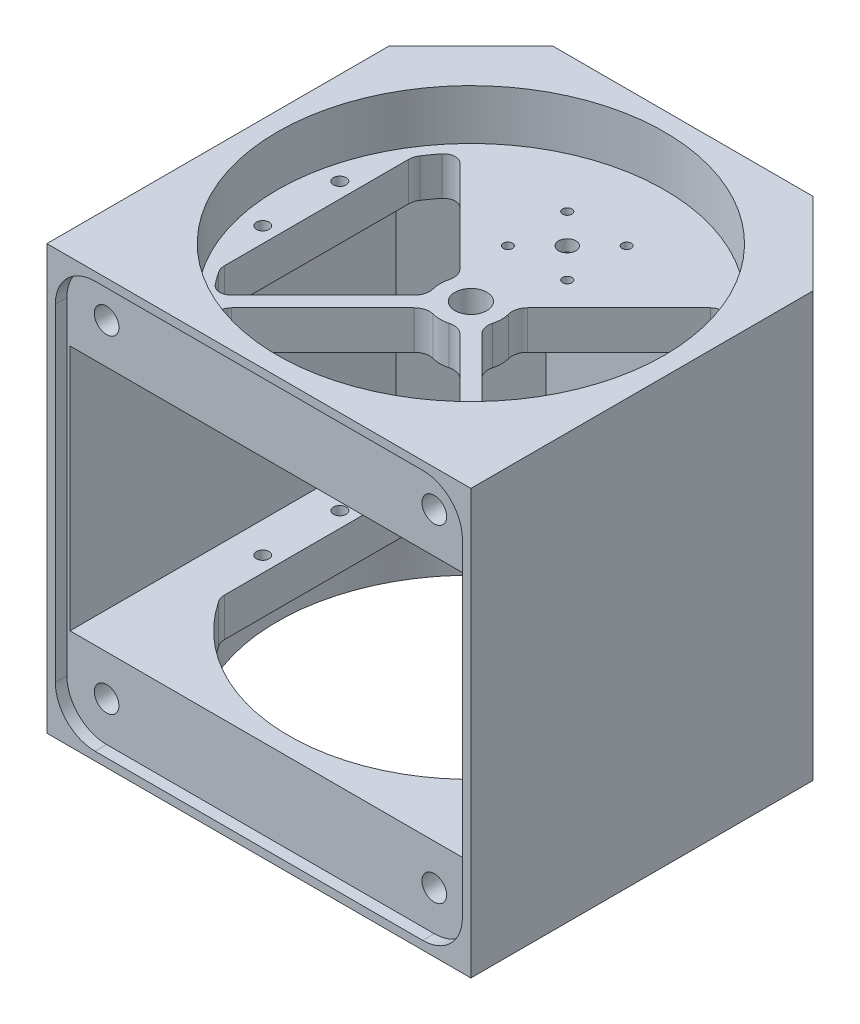
SolidWorks part; units mm, degrees
ref_plane "Front Plane" through (0, 0, 0) normal (0, 0, 1) x (1, 0, 0)
ref_plane "Top Plane" through (0, 0, 0) normal (0, 1, 0) x (1, 0, 0)
ref_plane "Right Plane" through (0, 0, 0) normal (1, 0, 0) x (0, 0, -1)
sketch "Sketch1" plane through (0, 0, 0) normal (0, 0, 1) x (1, 0, 0)
  line L5 (55, 55) -> (-55, 55)
  line L6 (55, 55) -> (55, -55)
  line L7 (55, -55) -> (-55, -55)
  line L12 (52.8, -42.5) -> (52.8, 42.5)
  line L13 (42.5, 52.8) -> (-42.5, 52.8)
  line L14 (-52.8, 42.5) -> (-52.8, -42.5)
  line L15 (-42.5, -52.8) -> (42.5, -52.8)
  line L16 (-55, 55) -> (-55, -55)
  line L17 (55, 55) -> (-55, -55) construction
  line L18 (55, -55) -> (-55, 55) construction
  arc A12 (52.8, 42.5) -> (42.5, 52.8) centre (42.5, 42.5) ccw
  arc A13 (-42.5, 52.8) -> (-52.8, 42.5) centre (-42.5, 42.5) ccw
  arc A14 (-52.8, -42.5) -> (-42.5, -52.8) centre (-42.5, -42.5) ccw
  arc A15 (42.5, -52.8) -> (52.8, -42.5) centre (42.5, -42.5) ccw
  point P0 (0, 0)
  dimension "D2" = 110
extrude "Boss-Extrude1" add sketch "Sketch1" against normal blind 3
sketch "Sketch2" plane through (0, -55, 0) normal (0, -1, 0) x (1, 0, 0)
  line L0 (55, -3) -> (55, -88.7868)
  line L1 (55, -88.7868) -> (33.7868, -110)
  line L2 (33.7868, -110) -> (-33.7868, -110)
  line L3 (-33.7868, -110) -> (-55, -88.7868)
  line L4 (-55, -88.7868) -> (-55, -3)
  line L5 (-55, -3) -> (55, -3) construction
  line L6 (-55, -3) -> (55, -3) construction
  line L7 (52, -3) -> (52, -87.5442)
  line L8 (-55, -3) -> (-55, 0) construction
  line L9 (-55, 0) -> (55, 0) construction
  line L10 (0, -110) -> (0, 0) construction
  line L11 (52, -87.5442) -> (32.5442, -107)
  line L12 (32.5442, -107) -> (-32.5442, -107)
  line L13 (-32.5442, -107) -> (-52, -87.5442)
  line L14 (-52, -87.5442) -> (-52, -3)
  line L15 (52, -3) -> (55, -3)
  line L16 (-55, -3) -> (-52, -3)
  circle A0 centre (0, -55) radius 50 construction
  dimension "D4" = 100
  dimension "D1" = 110
  dimension "D2" = 135
  dimension "D3" = 135
  dimension "D5" = 30
  dimension "D6" = 3
extrude "Boss-Extrude2" add sketch "Sketch2" against normal up to surface (110 mm away) up to face at (0, 55, -1.5)
sketch "Sketch3" plane through (0, -55, 0) normal (0, -1, 0) x (1, 0, 0)
  line L0 (-52, -3) -> (-52, -87.5442)
  line L1 (-52, -87.5442) -> (-32.5442, -107)
  line L2 (-32.5442, -107) -> (32.5442, -107)
  line L3 (32.5442, -107) -> (52, -87.5442)
  line L4 (52, -87.5442) -> (52, -3)
  line L5 (52, -3) -> (-52, -3)
  circle A0 centre (0, -55) radius 50.2
  dimension "D1" = 100.4
extrude "Boss-Extrude3" add sketch "Sketch3" against normal blind 3
sketch "Sketch4" plane through (0, -52, 0) normal (0, 1, 0) x (1, 0, 0)
  line L0 (11.2357, 3) -> (-11.2357, 3)
  circle A0 centre (0, 55) radius 50.2 construction
  circle A1 centre (0, 55) radius 50.2
  arc A2 (11.2357, 3) -> (-11.2357, 3) centre (0, 55) ccw
  circle A3 centre (0, 55) radius 53.2 construction
  dimension "D1" = 3
extrude "Boss-Extrude5" add sketch "Sketch4" along normal blind 10
sketch "Sketch5" plane through (0, -42, 0) normal (0, 1, 0) x (1, 0, 0)
  line L4 (52, 43.7643) -> (52, 66.2357)
  line L5 (11.2357, 107) -> (-11.2357, 107)
  line L6 (-52, 66.2357) -> (-52, 43.7643)
  line L7 (-11.2357, 3) -> (11.2357, 3)
  line L8 (52, 43.7643) -> (52, 66.2357)
  line L9 (11.2357, 107) -> (-11.2357, 107)
  line L10 (-52, 66.2357) -> (-52, 43.7643)
  line L11 (-11.2357, 3) -> (11.2357, 3)
  circle A0 centre (0, 55) radius 47.2
  circle A1 centre (0, 55) radius 50.2 construction
  arc A4 (11.2357, 3) -> (52, 43.7643) centre (0, 55) ccw
  arc A5 (52, 66.2357) -> (11.2357, 107) centre (0, 55) ccw
  arc A6 (-11.2357, 107) -> (-52, 66.2357) centre (0, 55) ccw
  arc A7 (-52, 43.7643) -> (-11.2357, 3) centre (0, 55) ccw
  arc A8 (11.2357, 3) -> (52, 43.7643) centre (0, 55) ccw
  arc A9 (52, 66.2357) -> (11.2357, 107) centre (0, 55) ccw
  arc A10 (-11.2357, 107) -> (-52, 66.2357) centre (0, 55) ccw
  arc A11 (-52, 43.7643) -> (-11.2357, 3) centre (0, 55) ccw
  dimension "D2" = 3
  dimension "D1" = 0
extrude "Boss-Extrude6" add sketch "Sketch5" along normal blind 2
sketch "Sketch11" plane through (0, -52, 0) normal (0, 1, 0) x (1, 0, 0)
  line L0 (-52, 43.7643) -> (-52, 3) construction
  line L1 (-52, 3) -> (-46.4799, 3) construction
  line L2 (-46.4799, 3) -> (-11.2357, 3) construction
  line L3 (-11.2357, 107) -> (-32.5442, 107) construction
  line L4 (-32.5442, 107) -> (-52, 87.5442) construction
  line L5 (-52, 87.5442) -> (-52, 66.2357) construction
  line L6 (52, 66.2357) -> (52, 87.5442) construction
  line L7 (52, 87.5442) -> (32.5442, 107) construction
  line L8 (32.5442, 107) -> (11.2357, 107) construction
  line L9 (11.2357, 3) -> (46.4799, 3) construction
  line L10 (46.4799, 3) -> (52, 3) construction
  line L11 (52, 3) -> (52, 43.7643) construction
  line L12 (-52, 43.7643) -> (-52, 3)
  line L13 (-52, 3) -> (-46.4799, 3)
  line L14 (-46.4799, 3) -> (-11.2357, 3)
  line L15 (-11.2357, 107) -> (-32.5442, 107)
  line L16 (-32.5442, 107) -> (-52, 87.5442)
  line L17 (-52, 87.5442) -> (-52, 66.2357)
  line L18 (52, 66.2357) -> (52, 87.5442)
  line L19 (52, 87.5442) -> (32.5442, 107)
  line L20 (32.5442, 107) -> (11.2357, 107)
  line L21 (11.2357, 3) -> (46.4799, 3)
  line L22 (46.4799, 3) -> (52, 3)
  line L23 (52, 3) -> (52, 43.7643)
  arc A0 (-52, 43.7643) -> (-11.2357, 3) centre (0, 55) ccw construction
  arc A1 (-11.2357, 107) -> (-52, 66.2357) centre (0, 55) ccw construction
  arc A2 (52, 66.2357) -> (11.2357, 107) centre (0, 55) ccw construction
  arc A3 (11.2357, 3) -> (52, 43.7643) centre (0, 55) ccw construction
  arc A4 (-52, 43.7643) -> (-11.2357, 3) centre (0, 55) ccw
  arc A5 (-11.2357, 107) -> (-52, 66.2357) centre (0, 55) ccw
  arc A6 (52, 66.2357) -> (11.2357, 107) centre (0, 55) ccw
  arc A7 (11.2357, 3) -> (52, 43.7643) centre (0, 55) ccw
extrude "Boss-Extrude14" add sketch "Sketch11" along normal blind 20
sketch "Sketch12" plane through (0, -40, 0) normal (0, 1, 0) x (1, 0, 0)
  line L4 (52, 43.7643) -> (52, 66.2357)
  line L5 (11.2357, 107) -> (-11.2357, 107)
  line L6 (-52, 66.2357) -> (-52, 43.7643)
  line L7 (-11.2357, 3) -> (11.2357, 3)
  line L8 (52, 43.7643) -> (52, 66.2357)
  line L9 (11.2357, 107) -> (-11.2357, 107)
  line L10 (-52, 66.2357) -> (-52, 43.7643)
  line L11 (-11.2357, 3) -> (11.2357, 3)
  circle A0 centre (0, 55) radius 47.2 construction
  circle A1 centre (0, 55) radius 47.2
  arc A4 (11.2357, 3) -> (52, 43.7643) centre (0, 55) ccw
  arc A5 (52, 66.2357) -> (11.2357, 107) centre (0, 55) ccw
  arc A6 (-11.2357, 107) -> (-52, 66.2357) centre (0, 55) ccw
  arc A7 (-52, 43.7643) -> (-11.2357, 3) centre (0, 55) ccw
  arc A8 (11.2357, 3) -> (52, 43.7643) centre (0, 55) ccw
  arc A9 (52, 66.2357) -> (11.2357, 107) centre (0, 55) ccw
  arc A10 (-11.2357, 107) -> (-52, 66.2357) centre (0, 55) ccw
  arc A11 (-52, 43.7643) -> (-11.2357, 3) centre (0, 55) ccw
  dimension "D1" = 0
extrude "Boss-Extrude16" add sketch "Sketch12" along normal up to surface (8 mm away) up to face at (38.445, -32, -93.445)
mirror "Mirror2" about plane through (0, 0, 0) normal (0, 1, 0) of "Boss-Extrude16", "Boss-Extrude14", "Boss-Extrude6", "Boss-Extrude5", "Boss-Extrude3"
sketch "Sketch13" plane through (0, 0, -3) normal (0, 0, 1) x (1, 0, 0)
  circle A0 centre (42.5, -42.5) radius 3.4195 construction
  circle A1 centre (-42.5, -42.5) radius 3.4195 construction
  circle A2 centre (-42.5, 42.5) radius 3.4195 construction
  circle A3 centre (42.5, 42.5) radius 3.4195 construction
  circle A4 centre (42.5, -42.5) radius 3.4195 construction
  circle A5 centre (-42.5, -42.5) radius 3.4195 construction
  circle A6 centre (-42.5, 42.5) radius 3.4195 construction
  circle A7 centre (42.5, 42.5) radius 3.4195 construction
  circle A8 centre (-42.5, 42.5) radius 3.2
  circle A9 centre (-42.5, -42.5) radius 3.2
  circle A10 centre (42.5, -42.5) radius 3.2
  circle A11 centre (42.5, 42.5) radius 3.2
  dimension "D1" = 6.4
extrude "Cut-Extrude2" cut sketch "Sketch13" against normal blind 15
sketch "Sketch14" plane through (0, 42, 0) normal (0, 1, 0) x (1, 0, 0)
  line L0 (0, 55) -> (0, -49945) construction
  line L1 (0, 55) -> (-35355.3391, 35410.3391) construction
  line L2 (0, 55) -> (35355.3391, 35410.3391) construction
  line L3 (-34.7597, 86.9313) -> (-6.8914, 59.063)
  line L4 (-31.9313, 89.7597) -> (-4.063, 61.8914)
  line L5 (-34.7597, 23.0687) -> (-6.8914, 50.937)
  line L6 (-4.063, 48.1086) -> (-31.9313, 20.2403)
  line L7 (6.8914, 50.937) -> (34.7597, 23.0687)
  line L8 (4.063, 48.1086) -> (31.9313, 20.2403)
  line L9 (4.063, 61.8914) -> (31.9313, 89.7597)
  line L10 (34.7597, 86.9313) -> (6.8914, 59.063)
  circle A0 centre (0, 55) radius 47.2 construction
  arc A1 (-34.7597, 23.0687) -> (-31.9313, 20.2403) centre (0, 55) ccw
  circle A2 centre (0, 55) radius 4.15
  arc A3 (-4.063, 48.1086) -> (4.063, 48.1086) centre (0, 55) ccw
  arc A4 (31.9313, 20.2403) -> (34.7597, 23.0687) centre (0, 55) ccw
  arc A5 (34.7597, 86.9313) -> (31.9313, 89.7597) centre (0, 55) ccw
  arc A6 (-31.9313, 89.7597) -> (-34.7597, 86.9313) centre (0, 55) ccw
  arc A7 (6.8914, 50.937) -> (6.8914, 59.063) centre (0, 55) ccw
  arc A8 (4.063, 61.8914) -> (-4.063, 61.8914) centre (0, 55) ccw
  arc A9 (-6.8914, 59.063) -> (-6.8914, 50.937) centre (0, 55) ccw
  dimension "D1" = 8.3
  dimension "D2" = 16
  dimension "D3" = 45
  dimension "D4" = 4
  dimension "D5" = 4
extrude "Boss-Extrude17" add sketch "Sketch14" against normal blind 10
fillet "Fillet1" radius 3 8 edges at (-34.7597, 37, -86.9313) (-31.9313, 37, -89.7597) (31.9313, 37, -89.7597) (34.7597, 37, -86.9313) (34.7597, 37, -23.0687) (31.9313, 37, -20.2403) (-31.9313, 37, -20.2403) (-34.7597, 37, -23.0687)
fillet "Fillet2" radius 4 8 edges at (4.063, 37, -61.8914) (-4.063, 37, -61.8914) (6.8914, 37, -59.063) (6.8914, 37, -50.937) (4.063, 37, -48.1086) (-4.063, 37, -48.1086) (-6.8914, 37, -50.937) (-6.8914, 37, -59.063)
sketch "Sketch15" plane through (0, 42, 0) normal (0, 1, 0) x (1, 0, 0)
  line L0 (-40, 80.0567) -> (-40, 29.9433)
  line L1 (0, -1000) -> (0, 49000) construction
  line L2 (40, 80.0567) -> (40, 29.9433)
  line L4 (44, 65) -> (-44, 65) construction
  line L5 (44, 65) -> (44, 45) construction
  line L6 (44, 45) -> (-44, 45) construction
  line L7 (-44, 65) -> (-44, 45) construction
  line L8 (44, 65) -> (-44, 45) construction
  line L9 (44, 45) -> (-44, 65) construction
  arc A0 (-36.9367, 84.3857) -> (-36.9367, 25.6143) centre (0, 55) ccw construction
  arc A1 (36.9367, 25.6143) -> (36.9367, 84.3857) centre (0, 55) ccw construction
  arc A2 (40, 29.9433) -> (40, 80.0567) centre (0, 55) ccw
  arc A3 (-40, 80.0567) -> (-40, 29.9433) centre (0, 55) ccw
  circle A4 centre (-44, 65) radius 1.65
  circle A5 centre (-44, 45) radius 1.65
  circle A6 centre (44, 45) radius 1.65
  circle A7 centre (44, 65) radius 1.65
  dimension "D4" = 3.3
  dimension "D1" = 80
  dimension "D2" = 88
  dimension "D3" = 20
extrude "Boss-Extrude18" add sketch "Sketch15" against normal blind 10
fillet "Fillet3" radius 4 2 edges at (-40, 37, -80.0567) (40, 37, -29.9433)
mirror "Mirror8" about plane through (0, 0, 0) normal (0, 1, 0) of "Boss-Extrude17"
fillet "Fillet4" radius 3 8 edges at (-31.9313, -37, -89.7597) (-34.7597, -37, -86.9313) (-34.7597, -37, -23.0687) (-31.9313, -37, -20.2403) (31.9313, -37, -20.2403) (34.7597, -37, -23.0687) (34.7597, -37, -86.9313) (31.9313, -37, -89.7597)
fillet "Fillet5" radius 4 8 edges at (-4.063, -37, -61.8914) (4.063, -37, -61.8914) (-6.8914, -37, -59.063) (-6.8914, -37, -50.937) (-4.063, -37, -48.1086) (4.063, -37, -48.1086) (6.8914, -37, -50.937) (6.8914, -37, -59.063)
mirror "Mirror9" about plane through (0, 0, 0) normal (0, 1, 0) of "Boss-Extrude18"
fillet "Fillet6" radius 4 4 edges at (-40, -37, -80.0567) (-40, -37, -29.9433) (40, -37, -29.9433) (40, -37, -80.0567)
sketch "Sketch16" plane through (0, 42, 0) normal (0, 1, 0) x (1, 0, 0)
  line L0 (29.6393, 87.4677) -> (5.9343, 63.7627) construction
  line L1 (-5.9343, 63.7627) -> (-29.6393, 87.4677) construction
  line L2 (29.6393, 87.4677) -> (5.9343, 63.7627)
  line L3 (-5.9343, 63.7627) -> (-29.6393, 87.4677)
  arc A0 (29.6393, 87.4677) -> (29.3857, 91.9367) centre (27.518, 89.589) ccw construction
  arc A1 (2.0706, 62.7274) -> (5.9343, 63.7627) centre (3.1058, 66.5911) ccw construction
  arc A2 (2.0706, 62.7274) -> (-2.0706, 62.7274) centre (0, 55) ccw construction
  arc A3 (-5.9343, 63.7627) -> (-2.0706, 62.7274) centre (-3.1058, 66.5911) ccw construction
  arc A4 (-29.3857, 91.9367) -> (-29.6393, 87.4677) centre (-27.518, 89.589) ccw construction
  arc A5 (29.3857, 91.9367) -> (-29.3857, 91.9367) centre (0, 55) ccw construction
  arc A6 (29.6393, 87.4677) -> (29.3857, 91.9367) centre (27.518, 89.589) ccw
  arc A7 (2.0706, 62.7274) -> (5.9343, 63.7627) centre (3.1058, 66.5911) ccw
  arc A8 (2.0706, 62.7274) -> (-2.0706, 62.7274) centre (0, 55) ccw
  arc A9 (-5.9343, 63.7627) -> (-2.0706, 62.7274) centre (-3.1058, 66.5911) ccw
  arc A10 (-29.3857, 91.9367) -> (-29.6393, 87.4677) centre (-27.518, 89.589) ccw
  arc A11 (29.3857, 91.9367) -> (-29.3857, 91.9367) centre (0, 55) ccw
extrude "Boss-Extrude19" add sketch "Sketch16" against normal blind 5
sketch "Sketch17" plane through (0, 37, 0) normal (0, -1, 0) x (1, 0, 0)
  line L0 (0, -55) -> (0, -80) construction
  line L2 (7.7, -72.3) -> (-7.7, -72.3) construction
  line L3 (7.7, -72.3) -> (7.7, -87.7) construction
  line L4 (7.7, -87.7) -> (-7.7, -87.7) construction
  line L5 (-7.7, -72.3) -> (-7.7, -87.7) construction
  line L6 (7.7, -72.3) -> (-7.7, -87.7) construction
  line L7 (7.7, -87.7) -> (-7.7, -72.3) construction
  circle A0 centre (0, -80) radius 2.25
  circle A1 centre (7.7, -72.3) radius 1.2
  circle A2 centre (7.7, -87.7) radius 1.2
  circle A3 centre (-7.7, -87.7) radius 1.2
  circle A4 centre (-7.7, -72.3) radius 1.2
  dimension "D2" = 4.5
  dimension "D3" = 2.4
  dimension "D1" = 25
  dimension "D4" = 15.4
extrude "Cut-Extrude3" cut sketch "Sketch17" against normal through all
sketch "Sketch18" plane through (0, 37, 0) normal (0, -1, 0) x (1, 0, 0)
  circle A0 centre (0, -80) radius 8.2
  dimension "D1" = 16.4
extrude "Cut-Extrude4" cut sketch "Sketch18" against normal blind 2
sketch "Sketch20" plane through (0, -42, 0) normal (0, -1, 0) x (1, 0, 0)
  line L0 (40, -78.8797) -> (40, -31.1203) construction
  line L1 (-40, -31.1203) -> (-40, -78.8797) construction
  line L2 (40, -78.8797) -> (40, -31.1203)
  line L3 (-40, -31.1203) -> (-40, -78.8797)
  arc A0 (-36.9367, -84.3857) -> (36.9367, -84.3857) centre (0, -55) ccw
  arc A1 (-36.9367, -25.6143) -> (36.9367, -25.6143) centre (0, -55) cw
  arc A2 (36.9367, -84.3857) -> (39.3333, -81.0908) centre (0, -55) ccw construction
  arc A3 (39.3333, -81.0908) -> (40, -78.8797) centre (36, -78.8797) ccw construction
  arc A4 (40, -31.1203) -> (39.3333, -28.9092) centre (36, -31.1203) ccw construction
  arc A5 (39.3333, -28.9092) -> (36.9367, -25.6143) centre (0, -55) ccw construction
  arc A6 (-36.9367, -25.6143) -> (-39.3333, -28.9092) centre (0, -55) ccw construction
  arc A7 (-39.3333, -28.9092) -> (-40, -31.1203) centre (-36, -31.1203) ccw construction
  arc A8 (-40, -78.8797) -> (-39.3333, -81.0908) centre (-36, -78.8797) ccw construction
  arc A9 (-39.3333, -81.0908) -> (-36.9367, -84.3857) centre (0, -55) ccw construction
  arc A10 (36.9367, -84.3857) -> (39.3333, -81.0908) centre (0, -55) ccw
  arc A11 (39.3333, -81.0908) -> (40, -78.8797) centre (36, -78.8797) ccw
  arc A12 (40, -31.1203) -> (39.3333, -28.9092) centre (36, -31.1203) ccw
  arc A13 (39.3333, -28.9092) -> (36.9367, -25.6143) centre (0, -55) ccw
  arc A14 (-36.9367, -25.6143) -> (-39.3333, -28.9092) centre (0, -55) ccw
  arc A15 (-39.3333, -28.9092) -> (-40, -31.1203) centre (-36, -31.1203) ccw
  arc A16 (-40, -78.8797) -> (-39.3333, -81.0908) centre (-36, -78.8797) ccw
  arc A17 (-39.3333, -81.0908) -> (-36.9367, -84.3857) centre (0, -55) ccw
  arc A18 (-29.3857, -91.9367) -> (29.3857, -91.9367) centre (0, -55) ccw construction
  arc A19 (29.3857, -18.0633) -> (-29.3857, -18.0633) centre (0, -55) ccw construction
extrude "Cut-Extrude5" cut sketch "Sketch20" against normal up to surface (10 mm away)
equation "\"D5@Sketch14\"=\"D4@Sketch14\""
